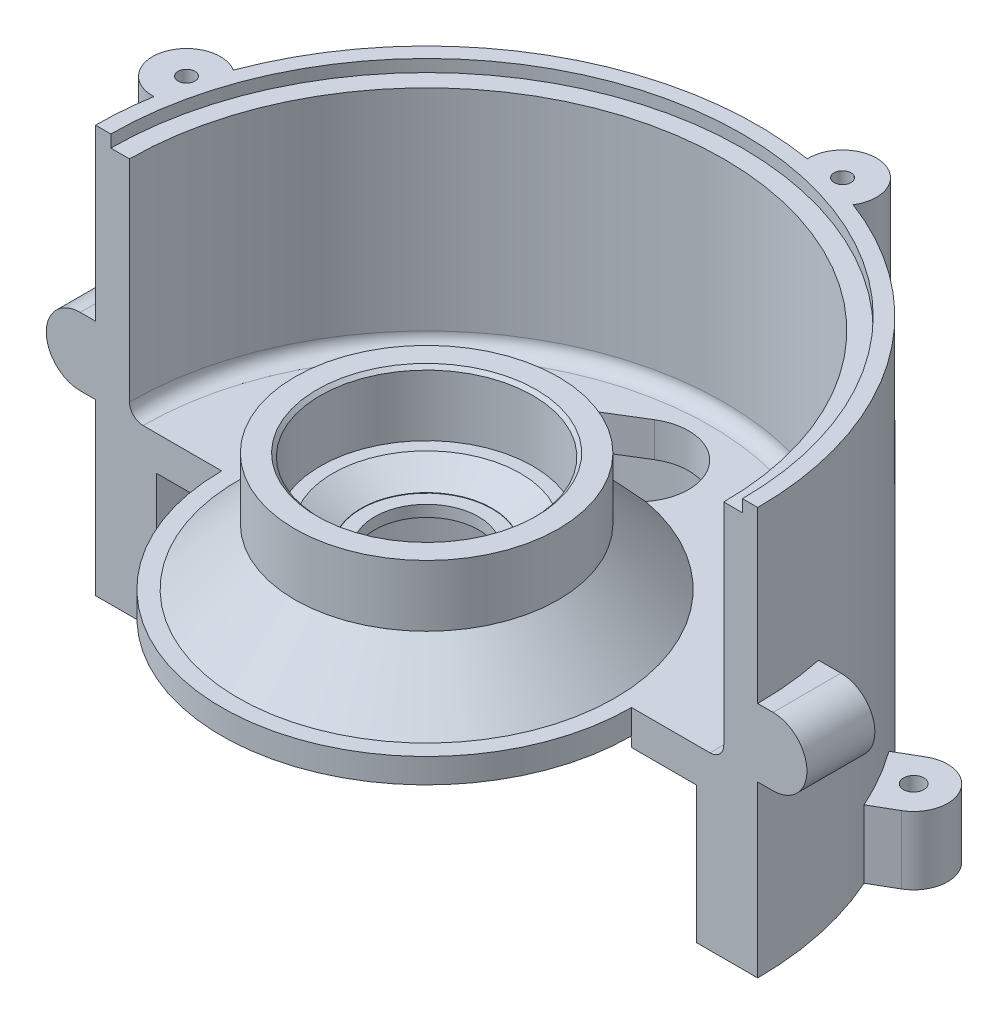
SolidWorks part; units mm, degrees
note: '?' marks a value the reader was unsure of.
ref_plane "Plano frontal" through (0, 0, 0) normal (0, 0, 1) x (1, 0, 0)
ref_plane "Plano superior" through (0, 0, 0) normal (0, 1, 0) x (1, 0, 0)
ref_plane "Plano direito" through (0, 0, 0) normal (1, 0, 0) x (0, 0, -1)
sketch "Esboço3" plane through (0, 0, 0) normal (0, 0, 1) x (1, 0, 0)
  line L2 (97.5, 79.8) -> (97.5, 11.3045)
  line L4 (79.5, 0) -> (60.3424, 0)
  line L5 (31.3, 25.96) -> (27.6265, 25.96)
  line L7 (60.2394, 2.95) -> (52, 2.95)
  line L8 (52, 2.95) -> (44, 10.95)
  line L9 (44, 10.95) -> (31, 10.95)
  line L10 (31, 10.95) -> (31, 13.7)
  line L11 (31, 13.7) -> (22.6, 13.7)
  line L12 (22.6, 13.7) -> (22.6, 17)
  line L13 (22.6, 17) -> (19.3, 17)
  line L14 (19.3, 17) -> (19.3, 17.7)
  line L15 (19.3, 17.7) -> (15.3, 17.7)
  line L16 (15.3, 17.7) -> (15.3, 21.05)
  line L17 (15.3, 21.05) -> (19.3, 21.05)
  line L18 (97.5, 79.8) -> (93, 79.8)
  line L19 (93, 79.8) -> (93, 76.2)
  line L20 (93, 76.2) -> (87.5, 76.2)
  line L21 (87.5, 76.2) -> (87.5, 14.2)
  line L22 (83.5, 10.2) -> (55.5, 10.2)
  line L23 (55.5, 10.2) -> (38.8, 26.9)
  line L24 (38.8, 26.9) -> (38.8, 44.96)
  line L25 (38.8, 44.96) -> (32.3, 44.96)
  line L26 (32.3, 44.96) -> (31.3, 43.96)
  line L27 (31.3, 43.96) -> (31.3, 25.96)
  line L29 (19.3, 21.05) -> (19.3, 21.2)
  line L30 (55, 0) -> (-55, 0) construction
  line L31 (27.6265, 25.96) -> (19.3, 21.2)
  line L33 (97.5, 0) -> (97.5, 11.3045)
  line L34 (97.5, 0) -> (97.5, -40.2)
  line L35 (97.5, -40.2) -> (79.5, -40.2)
  line L36 (79.5, -40.2) -> (79.5, 0)
  line L37 (0, 105.5372) -> (0, -70.3098) construction
  line L38 (60.3424, 0) -> (60.2394, 2.95)
  line L39 (60.3424, 0) -> (60.3265, 0.4569) construction
  line L40 (60.3424, 4.5188) -> (60.3424, 0) construction
  arc A1 (87.5, 14.2) -> (83.5, 10.2) centre (83.5, 14.2) cw
  dimension "D32" = 79.8
  dimension "D2" = 7.5
  dimension "D3" = 135
  dimension "D4" = 19
  dimension "D5" = 120
  dimension "D6" = 0.15
  dimension "D7" = 135
  dimension "D8" = 16
  dimension "D9" = 34.84
  dimension "D10" = 28
  dimension "D11" = 66
  dimension "D12" = 3.6
  dimension "D13" = 93
  dimension "D14" = 10
  dimension "D15" = 17.7
  dimension "D16" = 1
  dimension "D17" = 31.3
  dimension "D18" = 19.1576
  dimension "D19" = 52
  dimension "D20" = 44
  dimension "D21" = 135
  dimension "D22" = 31
  dimension "D23" = 22.6
  dimension "D24" = 19.3
  dimension "D25" = 15.3
  dimension "D26" = 2.75
  dimension "D27" = 3.3
  dimension "D28" = 0.7
  dimension "D29" = 3.35
  dimension "D30" = 79.5
  dimension "D31" = 97.5
  dimension "D33" = 2
ref_axis "Eixo1" through (0, -3.3221, 0) along (0, 1, 0)
revolve "Revolução2" add sketch "Esboço3" angle 180 about axis through (0, -3.3221, 0) along (0, 1, 0)
sketch "Esboço20" plane through (0, 0, 0) normal (0, 0, 1) x (1, 0, 0)
  line L0 (60.3424, 2.95) -> (60.3424, 10.2)
  line L1 (83.5, 10.2) -> (-83.5, 10.2) construction
  line L2 (60.3424, 10.2) -> (55.5, 10.2)
  line L3 (83.5, 10.2) -> (55.5, 10.2) construction
  line L4 (55.5, 10.2) -> (38.8, 26.9)
  line L5 (38.8, 26.9) -> (38.8, 44.96)
  line L6 (38.8, 44.96) -> (32.3, 44.96) construction
  line L7 (38.8, 44.96) -> (32.3, 44.96)
  line L8 (32.3, 44.96) -> (-32.3, 44.96) construction
  line L9 (32.3, 44.96) -> (31.3, 43.96)
  line L10 (31.3, 43.96) -> (31.3, 25.96)
  line L11 (31.3, 25.96) -> (27.6265, 25.96)
  line L12 (31.3, 25.96) -> (-31.3, 25.96) construction
  line L13 (27.6265, 25.96) -> (19.3, 21.2) construction
  line L14 (27.6265, 25.96) -> (19.3, 21.2)
  line L15 (19.3, 21.2) -> (19.3, 21.05)
  line L16 (19.3, 21.05) -> (15.3, 21.05)
  line L17 (15.3, 21.05) -> (15.3, 17.7)
  line L18 (15.3, 17.7) -> (19.3, 17.7)
  line L19 (19.3, 17.7) -> (19.3, 17)
  line L20 (19.3, 17) -> (22.6, 17)
  line L21 (22.6, 17) -> (22.6, 13.7)
  line L22 (22.6, 13.7) -> (31, 13.7)
  line L23 (31, 13.7) -> (31, 10.95)
  line L24 (31, 10.95) -> (44, 10.95)
  line L25 (44, 10.95) -> (52, 2.95)
  line L26 (52, 2.95) -> (60.3424, 2.95)
  line L27 (60.3424, 0) -> (60.3424, 2.95) construction
revolve "Revolução3" add sketch "Esboço20" angle 360 about axis through (0, -3.3221, 0) along (0, 1, 0)
sketch "Esboço4" plane through (0, 79.8, 0) normal (0, 1, 0) x (1, 0, 0)
  line L0 (25.8817, 96.5917) -> (-96.5917, 25.8817) construction
  line L1 (-96.5917, 25.8817) -> (-25.8817, -96.5917) construction
  line L2 (-25.8817, -96.5917) -> (96.5917, -25.8817) construction
  line L3 (96.5917, -25.8817) -> (25.8817, 96.5917) construction
  line L6 (-96.5917, 25.8817) -> (0, 0) construction
  line L7 (0, 0) -> (-25.8817, -96.5917) construction
  line L8 (96.5917, -25.8817) -> (0, 0) construction
  line L9 (0, 0) -> (25.8817, 96.5917) construction
  line L10 (0, 0) -> (0, 99.999) construction
  circle A0 centre (25.8817, 96.5917) radius 10
  circle A3 centre (-96.5917, 25.8817) radius 10
  dimension "D2" = 20
  dimension "D4" = 20
  dimension "D1" = 141.42
  dimension "D3" = 75
extrude "Ressalto-extrusão1" add sketch "Esboço4" against normal blind 35
sketch "Esboço5" plane through (0, -40.2, 0) normal (0, -1, 0) x (1, 0, 0)
  line L1 (0, 0) -> (0, -105) construction
  line L2 (10, -105) -> (10, -96.9858)
  line L3 (-10, -105) -> (-10, -96.9858)
  line L4 (10, -96.9858) -> (-10, -96.9858)
  arc A1 (10, -105) -> (-10, -105) centre (0, -105) cw
  arc A3 (-97.5, 0) -> (97.5, 0) centre (0, 0) ccw construction
  dimension "D2" = 10
  dimension "D1" = 105
extrude "Ressalto-extrusão2" add sketch "Esboço5" against normal blind 20
sketch "Esboço6" plane through (0, 79.8, 0) normal (0, 1, 0) x (1, 0, 0)
  circle A2 centre (25.8817, 96.5917) radius 2.5
  circle A3 centre (-96.5917, 25.8817) radius 2.5
  dimension "D1" = 5
extrude "Corte-extrusão1" cut sketch "Esboço6" against normal blind 15
sketch "Esboço9" plane through (0, 13.7, 0) normal (0, -1, 0) x (1, 0, 0)
  line L0 (0, 0) -> (18.7383, -18.7383) construction
  line L1 (-18.7383, -18.7383) -> (0, 0) construction
  line L2 (-18.7383, -18.7383) -> (18.7383, -18.7383) construction
  circle A2 centre (18.7383, -18.7383) radius 1.25
  circle A3 centre (-18.7383, -18.7383) radius 1.25
  circle A4 centre (-18.7383, 18.7383) radius 1.25
  circle A5 centre (18.7383, 18.7383) radius 1.25
  point P8 (0, 0)
  point P13 (4.0879, -3.0957)
  dimension "D2" = 26.5
  dimension "D1" = 26.5
  dimension "D3" = 2
extrude "Corte-extrusão3" cut sketch "Esboço9" against normal blind 6
sketch "Esboço10" plane through (0, 0, 0) normal (0, 0, 1) x (1, 0, 0)
  line L0 (93.1, -40.2) -> (93.1, 76.2)
  line L1 (93.1, 76.2) -> (93, 76.2) construction
  line L2 (91, 76.2) -> (90.9, 76.2) construction
  line L3 (93.1, 76.2) -> (90.9, 76.2)
  line L5 (90.9, 76.2) -> (90.9, -40.2)
  line L6 (90.9, -40.2) -> (93.1, -40.2)
  line L7 (79.5, -40.2) -> (97.5, -40.2) construction
  dimension "D2" = 2
  dimension "D3" = 0.1
extrude "Corte-extrusão4" [suppressed] cut sketch "Esboço10" against normal blind 3.5
sketch "Esboço11" plane through (0, 0, 0) normal (0, 0, 1) x (1, 0, 0)
  line L0 (-91, -38.7) -> (-91, 76.2)
  line L1 (-79.5, -40.2) -> (-97.5, -40.2) construction
  line L3 (-91, 76.2) -> (-93, 76.2)
  line L4 (-93, 76.2) -> (-93, -38.7)
  line L5 (-93, -38.7) -> (-91, -38.7)
  line L6 (-93, 79.8) -> (-93, 76.2) construction
  line L7 (-93, 76.2) -> (-87.5, 76.2) construction
  dimension "D1" = 2
  dimension "D2" = 1.5
extrude "Ressalto-extrusão5" [suppressed] add sketch "Esboço11" along normal blind 2
sketch "Esboço12" plane through (0, 0, 0) normal (0, 0, 1) x (1, 0, 0)
  line L0 (-124.1305, 19.8) -> (136.9824, 19.8) construction
  line L1 (-97.5, -40.2) -> (-97.5, 79.8) construction
  line L2 (-97.5, -40.2) -> (-97.5, 79.8) construction
  line L3 (-102, 9.8) -> (-102, 29.8) construction
  line L4 (-102, 29.8) -> (-87.5, 29.8)
  line L5 (-87.5, 76.2) -> (-87.5, 14.2) construction
  line L6 (-87.5, 29.8) -> (-87.5, 9.8)
  line L7 (-87.5, 9.8) -> (-102, 9.8)
  arc A1 (-102, 9.8) -> (-102, 29.8) centre (-102, 19.8) cw
  point P8 (-97.5, 19.8)
  dimension "D1" = 20
  dimension "D3" = 4.5
extrude "Ressalto-extrusão6" add sketch "Esboço12" against normal blind 20
sketch "Esboço13" plane through (0, 0, 0) normal (0, 0, 1) x (1, 0, 0)
  line L0 (102, 29.8) -> (102, 9.8) construction
  line L3 (-112, 19.8) -> (140.3594, 19.8) construction
  line L4 (102, 29.8) -> (93.1, 29.8)
  line L5 (93.1, 29.8) -> (93.1, 9.8)
  line L6 (93.1, 9.8) -> (102, 9.8)
  line L8 (97.5, -40.2) -> (97.5, 79.8) construction
  arc A0 (102, 9.8) -> (102, 29.8) centre (102, 19.8) ccw
  arc A2 (-102, 29.8) -> (-102, 9.8) centre (-102, 19.8) ccw construction
  dimension "D1" = 20
  dimension "D2" = 4.5
extrude "Ressalto-extrusão7" add sketch "Esboço13" against normal blind 20
sketch "Esboço41" plane through (0, 0, 0) normal (0, 1, 0) x (1, 0, 0)
  line L0 (-62.6914, 154.4823) -> (65.7089, -67.9134)
  line L1 (65.7089, -67.9134) -> (182.9572, 75.7902)
  line L2 (182.9572, 75.7902) -> (-62.6914, 154.4823)
extrude "Corte-extrusão13" [suppressed] cut sketch "Esboço41" against normal through all both and the other way through all
sketch "Esboço38" plane through (0, 0, 0) normal (0, 1, 0) x (1, 0, 0)
  line L0 (-100.9292, 133.1681) -> (28.6325, -91.2394)
  line L5 (28.6325, -91.2394) -> (-128.9348, -5.0413)
  line L6 (-128.9348, -5.0413) -> (-100.9292, 133.1681)
extrude "Corte-extrusão12" [suppressed] cut sketch "Esboço38" against normal through all both and the other way through all
sketch "Esboço45" plane through (0, 0, 0) normal (0, 0, 1) x (1, 0, 0)
  line L0 (-52, 2.95) -> (52, 2.95) construction
  line L1 (-44, 10.95) -> (-52, 2.95) construction
  line L2 (-60.3424, 0) -> (-60.2394, 2.95)
  line L3 (-60.2394, 2.95) -> (-52, 2.95)
  line L4 (-52, 2.95) -> (-44, 10.95)
  line L5 (-44, 10.95) -> (-31, 10.95)
  line L6 (-31, 10.95) -> (-31, -4.4212)
  line L7 (-31, -4.4212) -> (-60.3424, 0)
  line L8 (-44, 10.95) -> (44, 10.95) construction
  line L9 (-55.5, 10.2) -> (-38.8, 26.9)
  line L10 (-38.8, 26.9) -> (-87.5, 26.9)
  line L11 (-87.5, 76.2) -> (-87.5, 14.2) construction
  line L12 (-87.5, 26.9) -> (-87.5, 14.2)
  line L13 (-83.5, 10.2) -> (-55.5, 10.2)
  arc A0 (-87.5, 14.2) -> (-83.5, 10.2) centre (-83.5, 14.2) ccw
revolve "Corte-Revolução1" [suppressed] cut sketch "Esboço45" angle 360 about axis through (0, -3.3221, 0) along (0, 1, 0)
sketch "Esboço16" plane through (0, 76.2, 0) normal (0, 1, 0) x (1, 0, 0)
  circle A0 centre (0, 0) radius 93
extrude "Corte-extrusão6" cut sketch "Esboço16" along normal blind 10
sketch "Esboço17" [suppressed] plane through (0, -40.2, 0) normal (0, -1, 0) x (1, 0, 0)
  circle A0 centre (0, 0) radius 92.9674
  circle A1 centre (0, 0) radius 90.9674
  dimension "D1" = 2
extrude "Corte-extrusão7" [suppressed] cut sketch "Esboço17" against normal blind 1.5
ref_plane "Plano1" [suppressed] through (0, -20.1, 0) normal (0, -1, 0) x (-1, 0, 0)
sketch "Esboço24" [suppressed] plane through (0, -40.2, 0) normal (0, -1, 0) x (1, 0, 0)
  line L0 (-79.7733, -46.0481) -> (-0.0078, -92.1056)
  line L1 (-0.0078, -92.1056) -> (79.7619, -46.0554)
  line L2 (79.7619, -46.0554) -> (79.764, 0)
  line L3 (60.3424, 0) -> (79.5, 0) construction
  line L4 (79.764, 0) -> (79.5, 0)
  line L5 (79.5, 0) -> (79.4979, -45.903)
  line L6 (79.4979, -45.903) -> (-0.0042, -91.7987)
  line L7 (-0.0042, -91.7987) -> (-79.5021, -45.8957)
  line L8 (-79.5021, -45.8957) -> (-79.5, 0)
  line L9 (-79.5, 0) -> (-100.9327, 0) construction
  line L10 (-79.5, 0) -> (-79.7712, 0)
  line L11 (-60.3424, 0) -> (-79.5, 0) construction
  line L12 (-79.7712, 0) -> (-79.7733, -46.0481)
  arc A0 (-79.5, 0) -> (79.5, 0) centre (0, 0) ccw construction
  dimension "D1" = 120
  dimension "D2" = 120
  dimension "D3" = 120
extrude "Ressalto-extrusão11" [suppressed] add sketch "Esboço24" against normal blind 45
pattern_circular "PadrãoCircular1" count 2 every 60 about axis through (0, 0, 0) along (0, 1, 0) of "Ressalto-extrusão2"
sketch "Esboço46" plane through (0, -20.2, 0) normal (0, 1, 0) x (1, 0, 0)
  circle A0 centre (90.9327, 52.5) radius 3
  circle A1 centre (0, 105) radius 3
  circle A2 centre (-90.9327, 52.5) radius 3
  point P9 (0, 0)
  dimension "D1" = 6
  dimension "D2" = 3
extrude "Corte-extrusão14" cut sketch "Esboço46" against normal blind 30
sketch "Esboço47" plane through (0, 10.2, 0) normal (0, 1, 0) x (1, 0, 0)
  line L0 (0, 0) -> (0, 145.4495) construction
  line L1 (0, 0) -> (-78.1535, 135.3659) construction
  line L2 (-99.5929, 57.5) -> (0, 115) construction
  line L3 (-60.8273, 45.378) -> (-9.6981, 76.7756)
  line L4 (-45.8217, 19.3876) -> (5.3074, 50.7853)
  line L5 (-45.8217, 19.3876) -> (-60.8273, 45.378) construction
  line L6 (-9.6981, 76.7756) -> (5.3074, 50.7853) construction
  line L7 (-53.6769, 32.1793) -> (-1.8429, 63.9839) construction
  arc A0 (-85.9327, 61.1603) -> (-95.9327, 43.8397) centre (-90.9327, 52.5) ccw construction
  arc A1 (10, 105) -> (-10, 105) centre (0, 105) ccw construction
  arc A3 (-9.6981, 76.7756) -> (5.3074, 50.7853) centre (-1.8429, 63.9839) cw
  arc A4 (-45.8217, 19.3876) -> (-60.8273, 45.378) centre (-53.6769, 32.1793) cw
  point P18 (-35.2627, 61.0768)
  dimension "D1" = 30
  dimension "D2" = 60
  dimension "D3" = 30
  dimension "D4" = 55.5
extrude "Corte-extrusão15" cut sketch "Esboço47" against normal through all both and the other way through all
ref_axis "Eixo2" [suppressed] through (25.8817, 26.0295, -96.5917) along (0, 1, 0)?
ref_plane "Plano2" [suppressed] through (50.9771, 0, -80.7488) normal (0.5338, 0, -0.8456) x (-0.8456, 0, -0.5338)
ref_axis "Eixo3" [suppressed] through (-96.5917, 44.8, -25.8817) along (0, 1, 0)?
ref_plane "Plano3" [suppressed] through (-80.7488, 0, -50.9771) normal (-0.8456, 0, -0.5338) x (-0.5338, 0, 0.8456)
ref_plane "Plano5" [suppressed] through (-97.5, 0, 0) normal (-1, 0, 0) x (0, 0, 1)
ref_plane "Plano6" [suppressed] through (97.5, 0, 0) normal (-1, 0, 0) x (0, 1, 0)
sketch "Esboço36" plane through (0, 76.2, 0) normal (0, 1, 0) x (1, 0, 0)
  line L0 (87.5, 0) -> (93, 0)
  line L1 (-87.5, 0) -> (-93, 0)
  line L2 (-93, 0) -> (-87.5, 0) construction
  arc A0 (87.5, 0) -> (-87.5, 0) centre (0, 0) ccw
  arc A1 (93, 0) -> (-93, 0) centre (0, 0) ccw
extrude "Ressalto-extrusão19" [suppressed] add sketch "Esboço36" along normal through all
sketch "Esboço28" plane through (0, 0, 0) normal (1, 0, 0) x (0, 0, -1)
  line L0 (-38.8, 44.96) -> (-39.4535, 26.2465)
  line L1 (-38.8, 26.9) -> (-55.5, 10.2) construction
  line L2 (-39.4535, 26.2465) -> (-38.8, 26.2465)
  line L3 (-38.8, 26.2465) -> (-38.8, 44.96)
  dimension "D1" = 2
revolve "Revolução5" [suppressed] add sketch "Esboço28" angle 360 about axis through (0, -3.3221, 0) along (0, 1, 0)
sketch "Esboço35" [suppressed] plane through (0, 0, 0) normal (0, 0, 1) x (1, 0, 0)
  line L0 (27.8, 44.96) -> (26.965, 21.05)
  line L2 (26.965, 21.05) -> (38.8, 21.05)
  line L3 (38.8, 21.05) -> (38.8, 44.96)
  line L4 (38.8, 44.96) -> (27.8, 44.96)
  line L10 (26.965, 21.05) -> (15.3, 21.05) construction
  dimension "D1" = 2
  dimension "D2" = 11
revolve "Revolução8" [suppressed] add sketch "Esboço35" angle 360 about axis through (0, -3.3221, 0) along (0, 1, 0)
fillet "Filete22" [suppressed] radius 2
fillet "Filete29" [suppressed] radius 5
fillet "Filete25" [suppressed] radius 2
fillet "Filete28" [suppressed] radius 2
fillet "Filete34" [suppressed] radius 2
fillet "Filete variável2" [suppressed] radius 2?
fillet "Filete variável3" [suppressed] radius 2?
fillet "Filete variável6" [suppressed] radius 1?
fillet "Filete38" [suppressed] radius 5
fillet "Filete39" [suppressed] radius 2
fillet "Filete40" [suppressed] radius 2
fillet "Filete41" [suppressed] radius 2
fillet "Filete42" [suppressed] radius 5
scale "Escala1" [suppressed]
